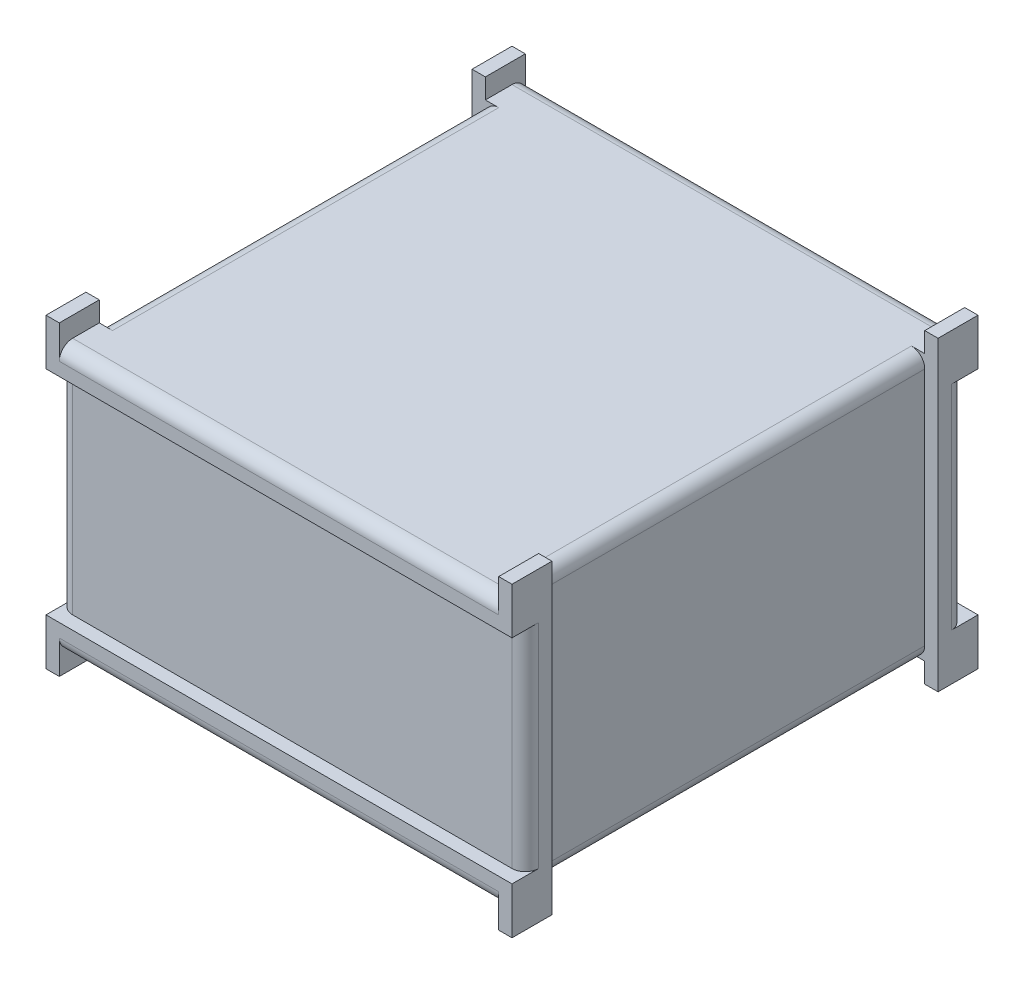
SolidWorks part; units mm, degrees
ref_plane "Front Plane" through (0, 0, 0) normal (0, 0, 1) x (1, 0, 0)
ref_plane "Top Plane" through (0, 0, 0) normal (0, 1, 0) x (1, 0, 0)
ref_plane "Right Plane" through (0, 0, 0) normal (1, 0, 0) x (0, 0, -1)
sketch "Sketch1" plane through (0, 0, 0) normal (0, 1, 0) x (1, 0, 0)
  line L1 (-13.2004, 10.0748) -> (21.7996, 10.0748)
  line L2 (-13.2004, 10.0748) -> (-13.2004, -24.9252)
  line L3 (-13.2004, -24.9252) -> (21.7996, -24.9252)
  line L4 (21.7996, 10.0748) -> (21.7996, -24.9252)
  dimension "D1" = 35
  dimension "D2" = 35
extrude "Boss-Extrude1" add sketch "Sketch1" along normal blind 23
sketch "Sketch2" plane through (0, 23, 0) normal (0, 1, 0) x (1, 0, 0)
  line L0 (21.7996, 10.0748) -> (-13.2004, 10.0748) construction
  line L1 (20.7996, -24.9252) -> (-12.2004, -24.9252)
  line L2 (20.7996, -24.9252) -> (20.7996, 10.0748)
  line L3 (20.7996, 10.0748) -> (-12.2004, 10.0748)
  line L4 (-12.2004, -24.9252) -> (-12.2004, 10.0748)
  line L5 (-13.2004, 10.0748) -> (-13.2004, -24.9252) construction
  dimension "D1" = 33
  dimension "D2" = 35
  dimension "D3" = 0
  dimension "D4" = 1
extrude "Cut-Extrude1" cut sketch "Sketch2" against normal blind 1.5
sketch "Sketch3" plane through (0, 0, 0) normal (0, -1, 0) x (1, 0, 0)
  line L1 (20.7996, -10.0748) -> (-12.2004, -10.0748)
  line L2 (20.7996, -10.0748) -> (20.7996, 24.9252)
  line L3 (20.7996, 24.9252) -> (-12.2004, 24.9252)
  line L4 (-12.2004, -10.0748) -> (-12.2004, 24.9252)
  line L6 (21.7996, 24.9252) -> (21.7996, -10.0748) construction
  line L7 (-13.2004, 24.9252) -> (21.7996, 24.9252) construction
  dimension "D1" = 33
  dimension "D2" = 35
  dimension "D3" = 1
  dimension "D4" = 0
extrude "Cut-Extrude2" cut sketch "Sketch3" against normal blind 1.5
fillet "Fillet2" radius 1 1 edges at (4.2996, 21.5, -10.0748)
fillet "Fillet3" radius 1 1 edges at (4.2996, 21.5, 24.9252)
fillet "Fillet4" radius 1 1 edges at (4.2996, 1.5, 24.9252)
fillet "Fillet5" radius 1 1 edges at (4.2996, 1.5, -10.0748)
sketch "Sketch5" plane through (0, 0, -10.0748) normal (0, 0, -1) x (-1, 0, 0)
  line L1 (13.2004, 3.509) -> (-21.7996, 3.509)
  line L2 (13.2004, 3.509) -> (13.2004, 19.509)
  line L3 (13.2004, 19.509) -> (-21.7996, 19.509)
  line L4 (-21.7996, 3.509) -> (-21.7996, 19.509)
  line L5 (12.2004, 20.5) -> (-20.7996, 20.5) construction
  line L6 (-21.7996, 23) -> (-21.7996, 0) construction
  dimension "D1" = 35
  dimension "D2" = 16
  dimension "D3" = 0.991
  dimension "D4" = 0
extrude "Cut-Extrude3" cut sketch "Sketch5" against normal blind 1
fillet "Fillet6" radius 1 1 edges at (-13.2004, 11.509, -9.0748)
fillet "Fillet7" radius 1 1 edges at (21.7996, 11.509, -9.0748)
sketch "Sketch6" plane through (0, 0, 24.9252) normal (0, 0, 1) x (1, 0, 0)
  line L0 (21.7996, 23) -> (21.7996, 0) construction
  line L1 (-13.2004, 19.509) -> (21.7996, 19.509)
  line L2 (-13.2004, 19.509) -> (-13.2004, 3.509)
  line L3 (-13.2004, 3.509) -> (21.7996, 3.509)
  line L4 (21.7996, 19.509) -> (21.7996, 3.509)
  line L5 (20.7996, 20.5) -> (-12.2004, 20.5) construction
  dimension "D1" = 0.991
  dimension "D2" = 35
  dimension "D3" = 16
extrude "Cut-Extrude4" cut sketch "Sketch6" against normal blind 1
fillet "Fillet8" radius 1 1 edges at (-13.2004, 11.509, 23.9252)
fillet "Fillet9" radius 1 1 edges at (21.7996, 11.509, 23.9252)
sketch "Sketch7" plane through (21.7996, 0, 0) normal (1, 0, 0) x (0, 0, -1)
  line L0 (-24.9252, 0) -> (10.0748, 0) construction
  line L1 (7.0748, 0) -> (-21.9252, 0)
  line L2 (7.0748, 0) -> (7.0748, 23)
  line L3 (7.0748, 23) -> (-21.9252, 23)
  line L4 (-21.9252, 0) -> (-21.9252, 23)
  line L5 (-22.9252, 19.509) -> (-22.9252, 3.509) construction
  dimension "D1" = 23
  dimension "D2" = 0
  dimension "D3" = 29
  dimension "D4" = 1
extrude "Cut-Extrude5" cut sketch "Sketch7" against normal blind 1
sketch "Sketch8" plane through (-13.2004, 0, -13.2004) normal (1, 0, 0) x (0, 0, -1)
  line L1 (-6.1256, 0) -> (-35.1256, 0)
  line L2 (-6.1256, 0) -> (-6.1256, 23)
  line L3 (-6.1256, 23) -> (-35.1256, 23)
  line L4 (-35.1256, 0) -> (-35.1256, 23)
  line L6 (-36.1256, 3.509) -> (-36.1256, 19.509) construction
  dimension "D1" = 23
  dimension "D2" = 1
  dimension "D3" = 29
extrude "Cut-Extrude6" cut sketch "Sketch8" along normal blind 1
fillet "Fillet10" radius 1 1 edges at (-12.2004, 21.5, 7.4252)
fillet "Fillet11" radius 1 1 edges at (-12.2004, 1.5, 7.4252)
fillet "Fillet12" radius 1 1 edges at (20.7996, 21.5, 7.4252)
fillet "Fillet13" radius 1 1 edges at (20.7996, 1.5, 7.4252)
